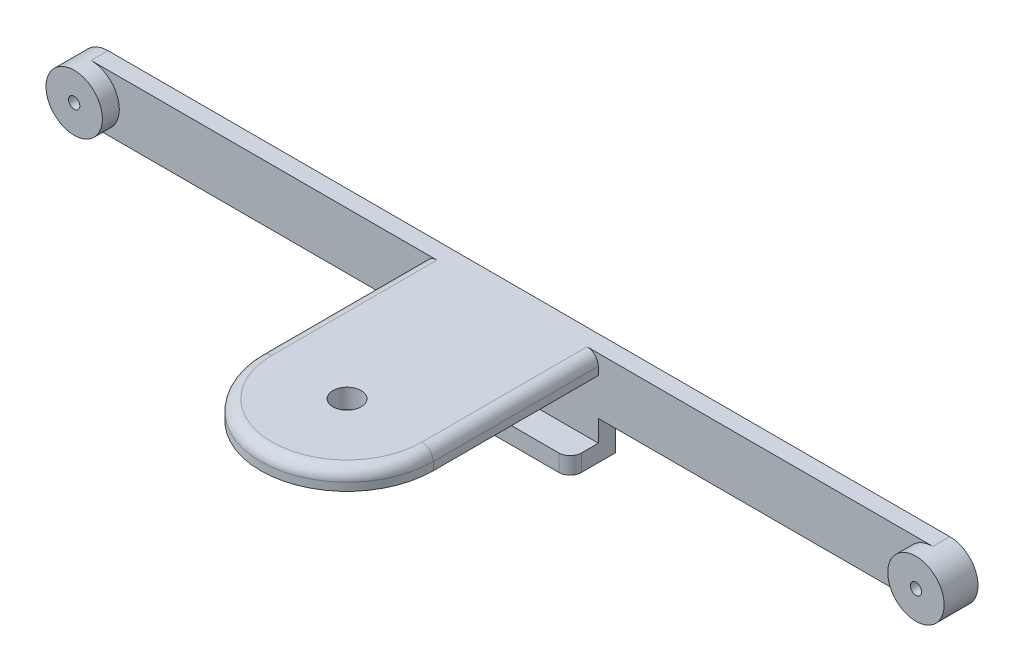
SolidWorks part; units mm, degrees
ref_plane "Front Plane" through (0, 0, 0) normal (0, 0, 1) x (1, 0, 0)
ref_plane "Top Plane" through (0, 0, 0) normal (0, 1, 0) x (1, 0, 0)
ref_plane "Right Plane" through (0, 0, 0) normal (1, 0, 0) x (0, 0, -1)
sketch "Sketch1" plane through (0, 0, 0) normal (0, 0, 1) x (1, 0, 0)
  line L1 (-64.2062, 9.215) -> (85.0238, 9.215)
  line L3 (-64.2062, -0.785) -> (85.0238, -0.785)
  arc A1 (85.0238, -0.785) -> (85.0238, 9.215) centre (85.0238, 4.215) ccw
  arc A2 (-64.2062, 9.215) -> (-64.2062, -0.785) centre (-64.2062, 4.215) ccw
  dimension "D1" = 149.23
  dimension "D2" = 10
  dimension "D3" = 149.23
extrude "Boss-Extrude1" add sketch "Sketch1" along normal blind 3
sketch "Sketch2" plane through (0, 0, 3) normal (0, 0, 1) x (1, 0, 0)
  circle A0 centre (-64.2062, 4.215) radius 5
  circle A1 centre (85.0238, 4.215) radius 5
  circle A2 centre (-64.2062, 4.215) radius 1
  circle A3 centre (85.0238, 4.215) radius 1
  dimension "D1" = 2
  dimension "D2" = 2
  dimension "D3" = 149.23
extrude "Boss-Extrude2" add sketch "Sketch2" along normal blind 3
sketch "Sketch5" plane through (0, 9.215, 0) normal (0, 1, 0) x (1, 0, 0)
  line L0 (-4.9012, -3) -> (25.7188, -3)
  line L1 (85.0238, -3) -> (-64.2062, -3) construction
  line L2 (10.4088, -3) -> (10.4088, 22.3394) construction
  line L3 (25.7188, -3) -> (25.7188, -16.94)
  line L4 (-4.9012, -3) -> (-4.9012, -16.94)
  line L5 (-4.9012, -16.94) -> (-4.9012, -32.25)
  line L6 (25.7188, -16.94) -> (25.7188, -32.25)
  arc A0 (-4.9012, -32.25) -> (25.7188, -32.25) centre (10.4088, -32.25) ccw
  circle A1 centre (10.4088, -32.25) radius 2.5
  point P5 (10.4088, -3)
  dimension "D7" = 5
  dimension "D1" = 13.94
  dimension "D2" = 13.94
  dimension "D3" = 30.62
  dimension "D4" = 74.615
  dimension "D5" = 15.31
  dimension "D6" = 15.31
sketch "Sketch7" plane through (0, 0, 6) normal (0, 0, 1) x (1, 0, 0)
  circle A0 centre (-64.2062, 4.215) radius 1
extrude "Cut-Extrude1" cut sketch "Sketch7" against normal blind 10
sketch "Sketch8" plane through (0, 0, 6) normal (0, 0, 1) x (1, 0, 0)
  circle A0 centre (85.0238, 4.215) radius 1
extrude "Cut-Extrude2" cut sketch "Sketch8" against normal blind 10
extrude "Boss-Extrude3" add sketch "Sketch5" against normal blind 3.41
sketch "Sketch9" plane through (0, -0.785, 0) normal (0, -1, 0) x (1, 0, 0)
  line L1 (-64.2062, 0) -> (85.0238, 0) construction
  line L7 (-64.2062, 3) -> (85.0238, 3) construction
  line L8 (-4.9012, 0) -> (25.7188, 0)
  line L9 (-4.9012, 0) -> (-4.9012, 3)
  line L10 (-4.9012, 3) -> (25.7188, 3)
  line L11 (25.7188, 0) -> (25.7188, 3)
  point P5 (10.4088, 0)
  dimension "D1" = 30.62
extrude "Boss-Extrude4" add sketch "Sketch9" along normal blind 3.8
sketch "Sketch10" plane through (0, -4.585, 0) normal (0, -1, 0) x (1, 0, 0)
  line L0 (25.7188, 32.25) -> (25.7188, 3) construction
  line L1 (-4.9012, 0) -> (25.7188, 0)
  line L2 (-4.9012, 0) -> (-4.9012, 8)
  line L3 (-4.9012, 8) -> (25.7188, 8)
  line L4 (25.7188, 0) -> (25.7188, 8)
  dimension "D1" = 8
extrude "Boss-Extrude5" add sketch "Sketch10" along normal blind 3
fillet "Fillet3" radius 2 5 edges at (25.7188, 9.215, 17.625) (10.4088, 9.215, 47.56) (-4.9012, 9.215, 17.625) (-4.9012, -6.085, 8) (25.7188, -6.085, 8)
